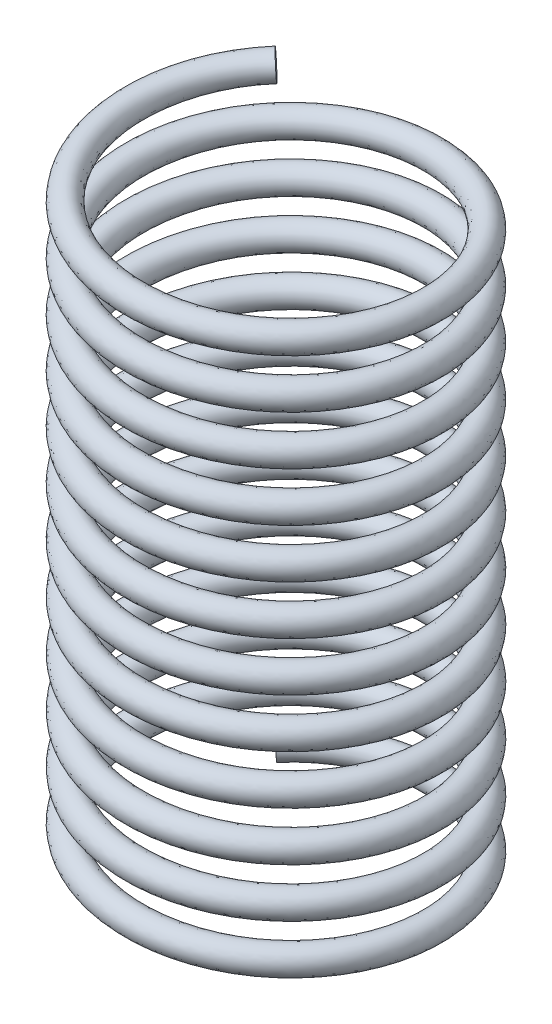
SolidWorks part; units mm, degrees
note: '?' marks a value the reader was unsure of.
material "AISI 1020 Steel, Cold Rolled"
ref_plane "Front Plane" through (0, 0, 0) normal (0, 0, 1) x (1, 0, 0)
ref_plane "Top Plane" through (0, 0, 0) normal (0, 1, 0) x (1, 0, 0)
ref_plane "Right Plane" through (0, 0, 0) normal (1, 0, 0) x (0, 0, -1)
sketch "Sketch2" plane through (0, 0, 0) normal (0, 1, 0) x (1, 0, 0)
  circle A0 centre (0, 0) radius 3.35
  dimension "D1" = 6.7
curve "Helix/Spiral1" [suppressed] pitch 2.5 height 30 turns 12
sweep "Sweep1" [suppressed] add path "Helix/Spiral1"? parameters "D3"=0.6
sketch "Sketch3" plane through (0, 0, 0) normal (0, 1, 0) x (1, 0, 0)
  circle A0 centre (0, 0) radius 3.35 construction
  circle A1 centre (0, 0) radius 3.35
curve "Helix/Spiral2" pitch 1.1 height 13.2 radius 3.35 left hand yes centre (0, 0, 0) axis (0, 1, 0) start towards (0, 0, 1)
sweep "Sweep2" add path "Helix/Spiral2" circular profile diameter 0.6 parameters "D3"=0.6
sketch "Sketch4" [suppressed] plane through (2.4845, 0.4173, -2.4845) normal (0.7022, 0.1179, -0.7022) x (-0.6945, -0.1042, -0.712)
  circle A0 centre (0.2056, 29.9777) radius 0.3 construction
  circle A1 centre (0.2056, 29.9777) radius 0.3 construction
  point P0 (0.2056, 30.2777)
ref_plane "Plane1" [suppressed] through (0, 30.2963, 0) normal (0, -1, 0) x (-1, 0, 0)
sketch "Sketch6" plane through (0.4865, 0.036, -0.4865) normal (0.7061, 0.0522, -0.7061) x (-0.7056, -0.0318, -0.7079)
  circle A1 centre (2.9291, 13.2819) radius 0.3
  circle A2 centre (2.9291, 13.2819) radius 0.3 construction
  point P0 (2.9291, 13.5819)
  dimension "D1" = 0
ref_plane "Plane2" through (0, 13.4994, 0) normal (0, 1, 0) x (1, 0, 0)
ref_axis "Axis1" [suppressed] through (0, 14.5191, 0) along (0, -1, 0)?
